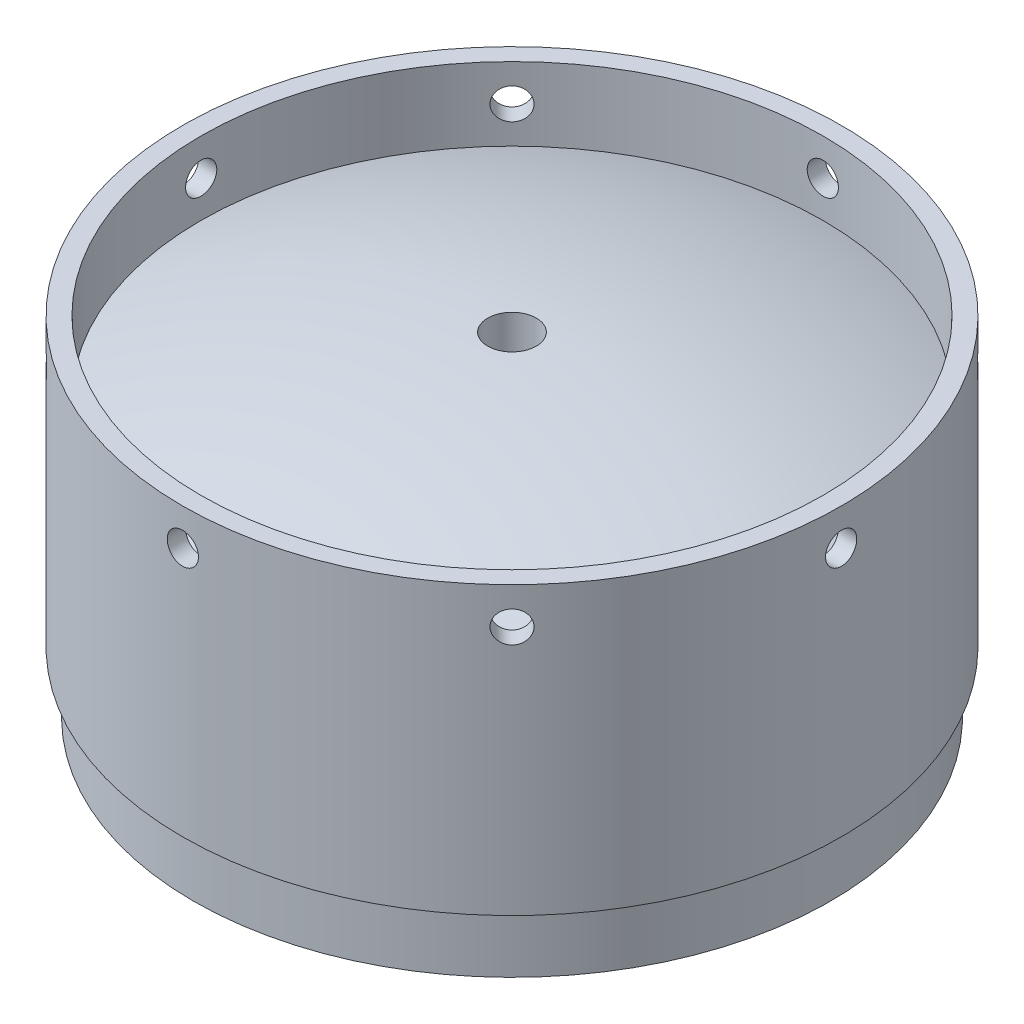
SolidWorks part; units mm, degrees
material "6061-T6 (SS)"
ref_plane "Front Plane" through (0, 0, 0) normal (0, 0, 1) x (1, 0, 0)
ref_plane "Top Plane" through (0, 0, 0) normal (0, 1, 0) x (1, 0, 0)
ref_plane "Right Plane" through (0, 0, 0) normal (1, 0, 0) x (0, 0, -1)
ref_axis "Axis1" through (0, 127.061, 0) along (0, -1, 0)
sketch "Sketch1" plane through (0, 0, 0) normal (0, 0, 1) x (1, 0, 0)
  line L0 (-57.15, 10.6249) -> (-57.15, 60.325)
  line L1 (-55.245, 9.525) -> (-57.15, 10.6249)
  line L2 (0, 127.061) -> (0, -81.9141) construction
  line L4 (-55.245, 9.525) -> (-55.245, 0)
  line L5 (-55.245, 0) -> (-53.975, 0)
  line L6 (55, 0) -> (-55, 0) construction
  line L7 (-53.975, 60.325) -> (-57.15, 60.325)
  line L8 (-57.15, 10.6249) -> (-55.245, 9.525)
  line L10 (-4.2164, 57.8559) -> (-4.2164, 50.8678)
  line L11 (-53.975, 47.625) -> (-53.975, 60.325)
  line L15 (-53.975, 0) -> (-53.975, 9.525)
  line L16 (-53.975, 9.525) -> (-50.7819, 27.6338)
  arc A0 (-50.7819, 27.6338) -> (-36.7422, 46.0132) centre (-31.7319, 27.6338) cw
  arc A1 (-36.7422, 46.0132) -> (-4.2164, 50.8678) centre (0, -88.7685) cw
  arc A3 (-53.975, 47.625) -> (-4.2164, 57.8559) centre (0, -88.7685) cw
  point P14 (-54.61, 0)
  point P15 (-37.8814, 47.625)
  point P16 (0, 0)
  point P18 (-53.975, 42.1458)
  point P20 (0, 0)
  point P22 (-53.975, 42.7789)
  point P23 (0, 0)
  point P25 (0, 0)
  point P26 (-4.2164, 57.0469)
  dimension "D5" = 19.05
  dimension "D6" = 139.7
  dimension "D7" = 146.685
  dimension "D8" = 50.8
  dimension "D2" = 170
  dimension "D3" = 9.525
  dimension "D4" = 1.27
  dimension "D9" = 12.7
  dimension "D10" = 3.175
  dimension "D13" = 4.2164
  dimension "D15" = 3.175
  dimension "D16" = 57.15
  dimension "D17" = 120
revolve "Revolve2" add sketch "Sketch1" angle 360 about axis through (0, 127.061, 0) along (0, -1, 0) region at (-56.3474, 35.4749, 0)
sketch "Sketch2" plane through (0, 0, 0) normal (0, 0, 1) x (1, 0, 0)
  line L0 (0, 127.061) -> (0, -81.9141) construction
  line L1 (0, 87.1374) -> (-97.8719, 87.1374)
  line L2 (0, 87.1374) -> (0, -26.2798)
  line L3 (0, -26.2798) -> (-97.8719, -26.2798)
  line L4 (-97.8719, 87.1374) -> (-97.8719, -26.2798)
revolve "Cut-Revolve1" [suppressed] cut sketch "Sketch2" angle 315 about axis through (0, 127.061, 0) along (0, -1, 0)
ref_plane "Plane1" through (0, 53.975, 0) normal (0, 1, 0) x (1, 0, 0)
ref_axis "Axis2" through (0, 53.975, -62.865) along (0, 0, 1)
hole_wizard "#3 (0.213) Diameter Hole1" positions "3DSketch3" profile "Sketch5" hole size "#3" standard "ANSI Inch"
sketch3d "3DSketch3"
  line L0 (0, 53.975, -62.865) -> (0, 53.975, 62.865) construction
  point P0 (0, 53.975, 57.15)
sketch "Sketch5" plane through (0, 53.975, 57.15) normal (1, 0, 0) x (0, -1, 0)
  line L0 (0, 0) -> (0, 13.3094)
  line L1 (0, 13.3094) -> (2.7051, 11.684)
  line L2 (2.7051, 11.684) -> (2.7051, 0)
  line L5 (2.7051, 0) -> (0, 0)
  line L10 (0, 13.3094) -> (-2.7051, 11.684) construction
  line L11 (0, -6.35) -> (0, 107.95) construction
  dimension "Hole Dia." = 5.4102
  dimension "Hole Depth" = 11.684
  dimension "Drill Angle" = 118
pattern_circular "CirPattern1" count 8 over 360 about axis through (0, 127.061, 0) along (0, -1, 0) of "#3 (0.213) Diameter Hole1"
cosmetic thread "Cosmetic Thread1" parameters "D2"=6.35
ref_plane "Plane2" through (0, 9.525, 0) normal (0, -1, 0) x (-1, 0, 0)
sketch "Sketch7" plane through (0, 9.525, 0) normal (0, -1, 0) x (-1, 0, 0)
  circle A0 centre (0, 0) radius 56.515
  dimension "D1" = 113.03
extrude "Boss-Extrude2" [suppressed] add sketch "Sketch7" against normal blind 41.91 separate body
combine bodies "Combine2" [suppressed] operation type subtract main body 113 bodies to subtract 110
